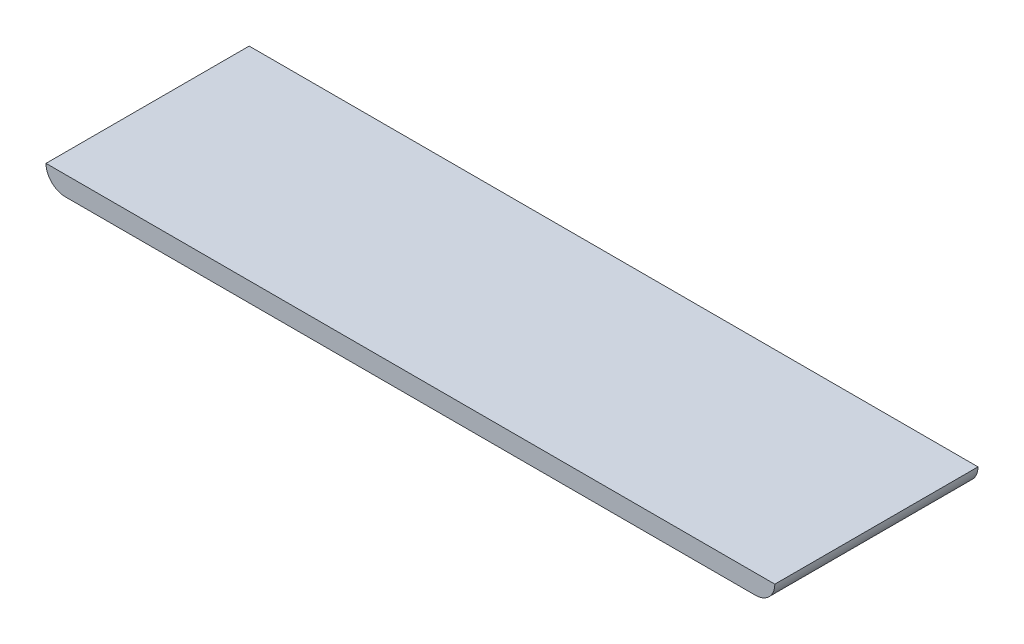
SolidWorks part; units mm, degrees
ref_plane "Спереди" through (0, 0, 0) normal (0, 0, 1) x (1, 0, 0)
ref_plane "Сверху" through (0, 0, 0) normal (0, 1, 0) x (1, 0, 0)
ref_plane "Справа" through (0, 0, 0) normal (1, 0, 0) x (0, 0, -1)
other "Configuration Table"
sketch "Эскиз1" plane through (0, 0, 0) normal (0, 1, 0) x (1, 0, 0)
  line L1 (-3, -31.5) -> (110, -31.5)
  line L2 (-3, -31.5) -> (-3, 0)
  line L3 (-3, 0) -> (110, 0)
  line L4 (110, -31.5) -> (110, 0)
extrude "Бобышка-Вытянуть1" add sketch "Эскиз1" along normal blind 3
fillet "tool_D3_R3_front_outer_corners" radius 3 2 edges at (-3, 0, 15.75) (110, 0, 15.75)
